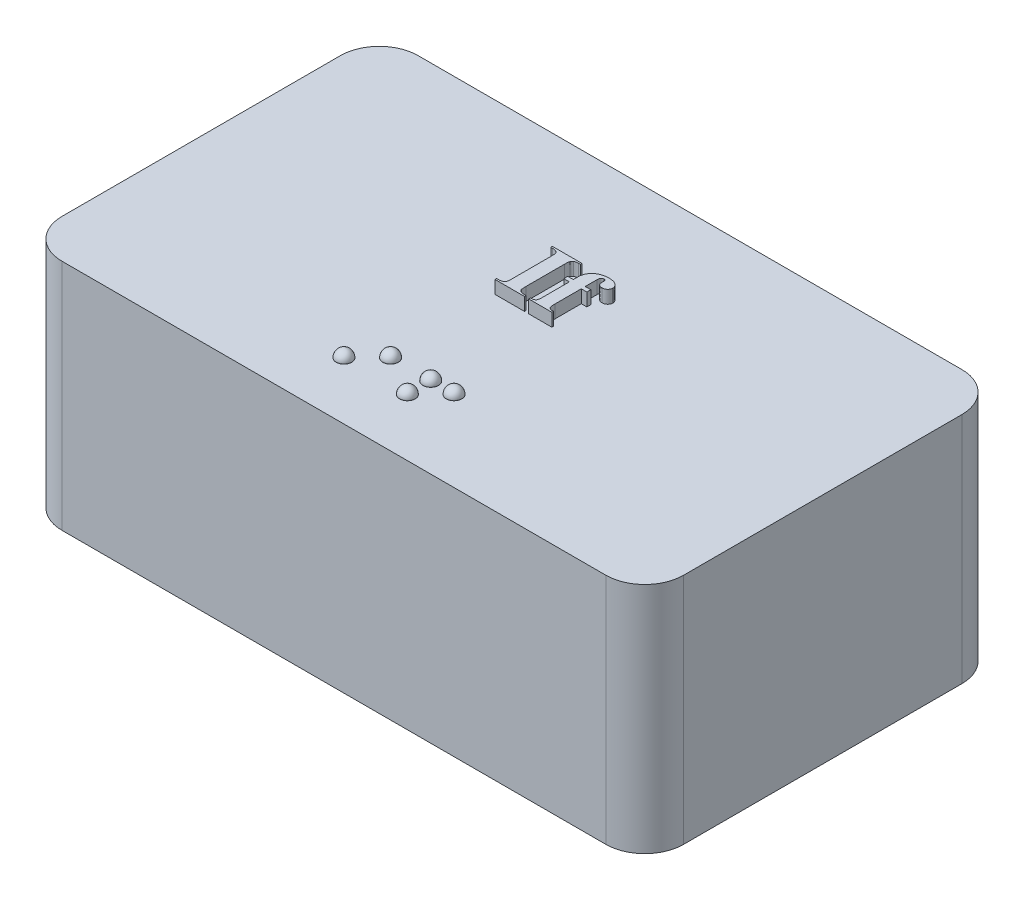
SolidWorks part; units mm, degrees
ref_plane "Front Plane" through (0, 0, 0) normal (0, 0, 1) x (1, 0, 0)
ref_plane "Top Plane" through (0, 0, 0) normal (0, 1, 0) x (1, 0, 0)
ref_plane "Right Plane" through (0, 0, 0) normal (1, 0, 0) x (0, 0, -1)
sketch "Sketch1" plane through (0, 0, 0) normal (0, 1, 0) x (1, 0, 0)
  line L1 (-30.48, 17.4625) -> (30.48, 17.4625)
  line L2 (-30.48, 17.4625) -> (-30.48, -17.4625)
  line L3 (-30.48, -17.4625) -> (30.48, -17.4625)
  line L4 (30.48, 17.4625) -> (30.48, -17.4625)
  line L5 (-30.48, 17.4625) -> (30.48, -17.4625) construction
  line L6 (-30.48, -17.4625) -> (30.48, 17.4625) construction
  point P0 (0, 0)
  dimension "D1" = 60.96
  dimension "D2" = 34.925
extrude "Boss-Extrude1" add sketch "Sketch1" along normal blind 22.86
sketch "Sketch2" plane through (0, 22.86, 0) normal (0, 1, 0) x (1, 0, 0)
  line L0 (-30.48, 17.4625) -> (-30.48, 0.9525) construction
  line L1 (-30.48, 17.4625) -> (-30.48, -17.4625) construction
  line L2 (-30.48, 0.9525) -> (30.48, 0.9525) construction
  line L3 (30.48, -17.4625) -> (30.48, 17.4625) construction
  line L4 (-30.48, 0.9525) -> (-30.48, -9.525) construction
  text T0 "<b>If</b>" font "Times New Roman" height in points 23
  dimension "D1" = 16.51
sketch "Sketch3" plane through (0, 22.86, 0) normal (0, 1, 0) x (1, 0, 0)
  line L0 (-30.48, 17.4625) -> (-30.48, 0.9525) construction
  line L1 (-30.48, 17.4625) -> (-30.48, -17.4625) construction
  line L2 (1.5838, -11.8411) -> (1.5838, -14.1271) construction
  line L3 (-17.0852, -9.5551) -> (-14.7992, -9.5551) construction
  line L4 (-17.0852, -9.5551) -> (-17.0852, -11.8411) construction
  line L5 (-14.7992, -9.5551) -> (-14.7992, -11.8411) construction
  line L6 (-17.0852, -9.5551) -> (-10.8622, -9.5551) construction
  line L7 (-10.8622, -9.5551) -> (-8.5762, -9.5551) construction
  line L8 (-8.5762, -9.5551) -> (-8.5762, -11.8411) construction
  line L9 (-10.8622, -9.5551) -> (-10.8622, -11.8411) construction
  line L10 (-10.8622, -11.8411) -> (-10.8622, -14.1271) construction
  line L11 (-10.8622, -9.5551) -> (-4.6392, -9.5551) construction
  line L12 (-4.6392, -9.5551) -> (1.5838, -9.5551) construction
  line L13 (1.5838, -9.5551) -> (1.5838, -11.8411) construction
  line L14 (1.5838, -9.5551) -> (3.8698, -9.5551) construction
  line L15 (1.5838, -9.5551) -> (7.8068, -9.5551) construction
  line L16 (7.8068, -9.5551) -> (7.8068, -14.1271) construction
  line L17 (7.8068, -11.8411) -> (10.0928, -11.8411) construction
  line L18 (7.8068, -9.5551) -> (14.0298, -9.5551) construction
  line L19 (14.0298, -9.5551) -> (14.0298, -11.8411) construction
  line L20 (14.0298, -11.8411) -> (14.0298, -14.1271) construction
  line L21 (14.0298, -11.8411) -> (16.3158, -11.8411) construction
  line L22 (14.0298, -9.5551) -> (20.2528, -9.5551) construction
  line L23 (20.2528, -9.5551) -> (22.5388, -9.5551) construction
  line L24 (22.5388, -9.5551) -> (22.5388, -11.8411) construction
  line L25 (26.4758, -9.5551) -> (26.4758, -11.8411) construction
  line L26 (26.4758, -11.8411) -> (26.4758, -14.1271) construction
  line L27 (20.2528, -9.5551) -> (26.4758, -9.5551) construction
  line L28 (26.4758, -9.5551) -> (32.6988, -9.5551) construction
  line L29 (32.6988, -9.5551) -> (32.6988, -11.8411) construction
  line L30 (32.6988, -11.8411) -> (32.6988, -14.1271) construction
  line L31 (32.6988, -11.8411) -> (34.9848, -11.8411) construction
  line L32 (32.6988, -9.5551) -> (38.9218, -9.5551) construction
  line L33 (38.9218, -9.5551) -> (41.2078, -9.5551) construction
  line L34 (41.2078, -9.5551) -> (41.2078, -11.8411) construction
  line L35 (-30.48, 0.9525) -> (-30.48, -8.5725) construction
  line L36 (-30.48, -8.5725) -> (30.48, -8.5725) construction
  line L37 (30.48, -17.4625) -> (30.48, 17.4625) construction
  line L38 (1.5838, -11.8411) -> (3.8698, -11.8411) construction
  line L39 (14.0298, -14.1271) -> (16.3158, -14.1271) construction
  line L40 (26.4758, -11.8411) -> (28.7618, -11.8411) construction
  line L41 (34.9848, -11.8411) -> (34.9848, -9.5551) construction
  line L42 (-14.7992, -11.8411) -> (-14.7992, -14.1271) construction
  line L43 (-4.6392, -9.5551) -> (-2.3532, -9.5551) construction
  line L44 (-2.3532, -9.5551) -> (-2.3532, -11.8411) construction
  line L45 (-2.3532, -11.8411) -> (-4.6392, -11.8411) construction
  line L46 (20.2528, -9.5551) -> (20.2528, -11.8411) construction
  line L47 (20.2528, -11.8411) -> (20.2528, -14.1271) construction
  line L48 (38.9218, -9.5551) -> (38.9218, -11.8411) construction
  line L49 (38.9218, -11.8411) -> (38.9218, -14.1271) construction
  circle A12 centre (1.5838, -9.5551) radius 0.762
  circle A45 centre (-2.3532, -9.5551) radius 0.762
  circle A46 centre (-4.6392, -11.8411) radius 0.762
  circle A58 centre (1.5838, -11.8411) radius 0.762
  circle A59 centre (3.8698, -9.5551) radius 0.762
  dimension "D9" = 6.223
  dimension "D10" = 6.223
  dimension "D11" = 2.286
  dimension "D12" = 6.223
  dimension "D13" = 2.286
  dimension "D15" = 2.286
  dimension "D16" = 6.223
  dimension "D20" = 6.223
  dimension "D21" = 6.223
  dimension "D22" = 2.286
  dimension "D25" = 6.223
  dimension "D26" = 2.286
  dimension "D28" = 16.51
  dimension "D31" = 2.286
  dimension "D32" = 2.286
  dimension "D19" = 2.286
  dimension "D1" = 2.286
  dimension "D2" = 2.286
  dimension "D3" = 2.286
  dimension "D4" = 6.223
  dimension "D5" = 2.286
  dimension "D6" = 2.286
  dimension "D7" = 2.286
  dimension "D8" = 6.223
  dimension "D14" = 2.286
  dimension "D17" = 2.286
  dimension "D18" = 2.286
  dimension "D23" = 2.286
  dimension "D24" = 2.286
  dimension "D27" = 2.286
  dimension "D29" = 9.525
  dimension "D30" = 2.286
extrude "Boss-Extrude3" add sketch "Sketch2" along normal blind 1.27
extrude "Boss-Extrude4" add sketch "Sketch3" along normal blind 0.0254
sketch "Sketch6" plane through (0, 0, 0) normal (0, -1, 0) x (-1, 0, 0)
  line L0 (30.48, -17.4625) -> (30.48, 0) construction
  line L1 (30.48, 17.4625) -> (30.48, -17.4625) construction
  line L2 (30.48, 0) -> (25.4, 0) construction
  line L3 (-30.48, -17.4625) -> (-30.48, 0) construction
  line L4 (-30.48, -17.4625) -> (-30.48, 17.4625) construction
  line L5 (-30.48, 0) -> (-25.4, 0) construction
  circle A0 centre (25.4, 0) radius 3.15
  circle A1 centre (-25.4, 0) radius 3.15
  dimension "D1" = 5.08
  dimension "D2" = 5.08
extrude "Cut-Extrude1" cut sketch "Sketch6" against normal blind 3.25
sketch "Sketch7" plane through (0, 0, 0) normal (0, -1, 0) x (-1, 0, 0)
  line L1 (20.828, -11.43) -> (-20.828, -11.43)
  line L2 (20.828, -11.43) -> (20.828, 11.43)
  line L3 (20.828, 11.43) -> (-20.828, 11.43)
  line L4 (-20.828, -11.43) -> (-20.828, 11.43)
  line L5 (20.828, -11.43) -> (-20.828, 11.43) construction
  line L6 (20.828, 11.43) -> (-20.828, -11.43) construction
  point P0 (0, 0)
  dimension "D1" = 41.656
  dimension "D2" = 22.86
extrude "Cut-Extrude2" cut sketch "Sketch7" against normal blind 17.78
fillet "Fillet2" radius 3.81 4 edges at (-30.48, 11.43, -17.4625) (30.48, 11.43, -17.4625) (30.48, 11.43, 17.4625) (-30.48, 11.43, 17.4625)
sketch "Sketch8" plane through (0, 17.78, 0) normal (0, -1, 0) x (1, 0, 0)
  line L1 (-20.828, 11.43) -> (-12.7, 11.43)
  line L2 (-20.828, 11.43) -> (-20.828, 3.302)
  line L3 (-20.828, 3.302) -> (-12.7, 3.302)
  line L4 (-12.7, 11.43) -> (-12.7, 3.302)
  line L5 (20.828, -11.43) -> (12.7, -11.43)
  line L6 (20.828, -11.43) -> (20.828, -3.302)
  line L7 (20.828, -3.302) -> (12.7, -3.302)
  line L8 (12.7, -11.43) -> (12.7, -3.302)
  dimension "D1" = 8.128
  dimension "D2" = 8.128
  dimension "D3" = 8.128
  dimension "D4" = 8.128
extrude "Boss-Extrude5" add sketch "Sketch8" along normal blind 13.97
sketch "Sketch9" plane through (0, 3.81, 0) normal (0, -1, 0) x (-1, 0, 0)
  line L0 (12.7, -7.366) -> (20.828, -7.366) construction
  line L1 (12.7, -3.302) -> (12.7, -11.43) construction
  line L2 (20.828, -11.43) -> (20.828, -3.302) construction
  line L3 (-12.7, 7.366) -> (-20.828, 7.366) construction
  line L4 (-12.7, 3.302) -> (-12.7, 11.43) construction
  line L5 (-20.828, 11.43) -> (-20.828, 3.302) construction
  circle A0 centre (16.764, -7.366) radius 1.7018
  circle A1 centre (-16.764, 7.366) radius 1.7018
extrude "Cut-Extrude3" cut sketch "Sketch9" against normal blind 12.7
dome "Dome51" faces to dome 1 distance 0.762 reverse direction no elliptical dome no face at (-4.6392, 22.8854, 12.6031) parameters "D1"=0.762
dome "Dome52" faces to dome 1 distance 0.762 reverse direction no elliptical dome no face at (-2.3532, 22.8854, 10.3171) parameters "D1"=0.762
dome "Dome53" faces to dome 1 distance 0.762 reverse direction no elliptical dome no face at (1.5838, 22.8854, 10.3171) parameters "D1"=0.762
dome "Dome54" faces to dome 1 distance 0.762 reverse direction no elliptical dome no face at (1.5838, 22.8854, 12.6031) parameters "D1"=0.762
dome "Dome55" faces to dome 1 distance 0.762 reverse direction no elliptical dome no face at (3.8698, 22.8854, 10.3171) parameters "D1"=0.762
